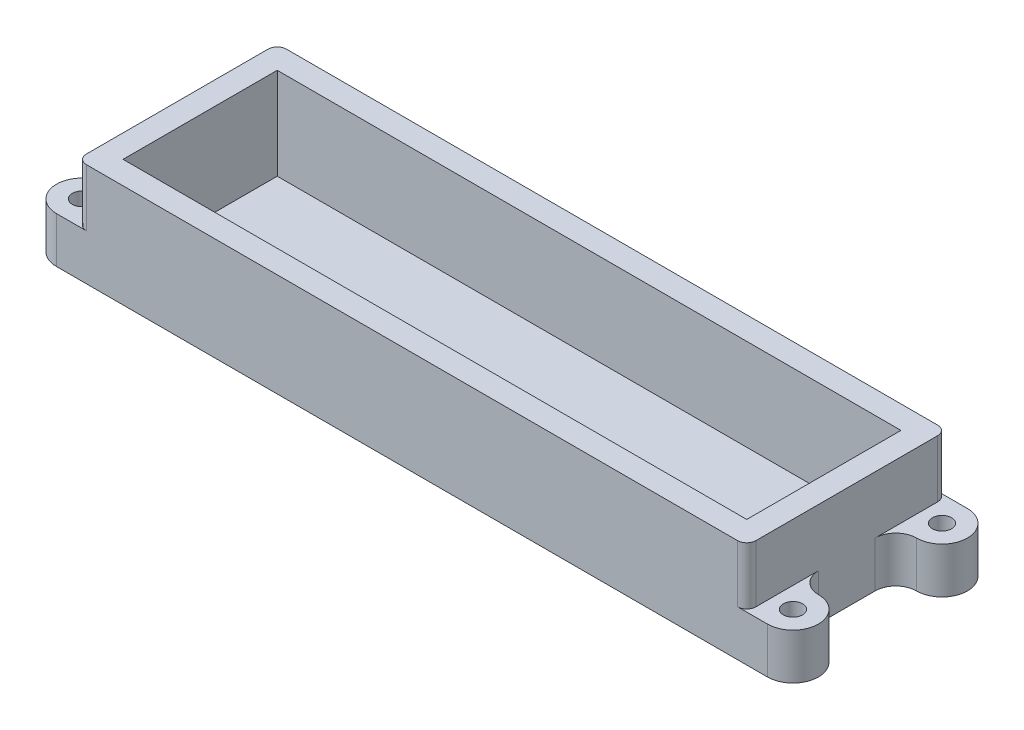
SolidWorks part; units mm, degrees
ref_plane "Front Plane" through (0, 0, 0) normal (0, 0, 1) x (1, 0, 0)
ref_plane "Top Plane" through (0, 0, 0) normal (0, 1, 0) x (1, 0, 0)
ref_plane "Right Plane" through (0, 0, 0) normal (1, 0, 0) x (0, 0, -1)
sketch "Sketch1" plane through (0, 0, 0) normal (0, 1, 0) x (1, 0, 0)
  line L0 (0, 0) -> (-5.725, 0)
  line L1 (0, 0) -> (185.4, 0)
  line L2 (0, 0) -> (0, 55.4)
  line L3 (0, 55.4) -> (185.4, 55.4)
  line L4 (185.4, 0) -> (185.4, 55.4)
  line L5 (6.35, 49.05) -> (179.05, 49.05)
  line L6 (6.35, 49.05) -> (6.35, 6.35)
  line L7 (6.35, 6.35) -> (179.05, 6.35)
  line L8 (179.05, 49.05) -> (179.05, 6.35)
  line L9 (0, 19.85) -> (0, 0)
  line L10 (6.35, 27.7) -> (10.8808, 27.7) construction
  line L11 (92.7, 49.05) -> (92.7, 30.1082) construction
  line L12 (0, 55.4) -> (-5.725, 55.4)
  line L13 (0, 35.55) -> (0, 55.4)
  line L14 (185.4, 19.85) -> (185.4, 0)
  line L15 (185.4, 0) -> (191.125, 0)
  line L16 (185.4, 35.55) -> (185.4, 55.4)
  line L17 (185.4, 55.4) -> (191.125, 55.4)
  circle A0 centre (42.7, 20.7) radius 3.175
  circle A1 centre (142.7, 20.7) radius 3.175
  arc A2 (-5.725, 0) -> (-5.725, 14.125) centre (-5.725, 7.0625) cw
  arc A3 (-5.725, 14.125) -> (0, 19.85) centre (-5.725, 19.85) ccw
  arc A4 (-5.725, 41.275) -> (0, 35.55) centre (-5.725, 35.55) cw
  arc A5 (-5.725, 55.4) -> (-5.725, 41.275) centre (-5.725, 48.3375) ccw
  circle A6 centre (-5.725, 7.0625) radius 2.667
  circle A7 centre (-5.725, 48.3375) radius 2.667
  circle A8 centre (191.125, 7.0625) radius 2.667
  circle A9 centre (191.125, 48.3375) radius 2.667
  arc A10 (191.125, 14.125) -> (185.4, 19.85) centre (191.125, 19.85) cw
  arc A11 (191.125, 0) -> (191.125, 14.125) centre (191.125, 7.0625) ccw
  arc A12 (191.125, 41.275) -> (185.4, 35.55) centre (191.125, 35.55) ccw
  arc A13 (191.125, 55.4) -> (191.125, 41.275) centre (191.125, 48.3375) cw
  point P9 (92.7, 49.05)
  point P10 (6.35, 27.7)
  point P11 (92.7, 27.7)
  point P44 (180.2689, 6.35)
  point P45 (181.9468, 42.173)
  dimension "D7" = 6.35
  dimension "D12" = 5.334
  dimension "D1" = 172.7
  dimension "D2" = 6.35
  dimension "D3" = 6.35
  dimension "D4" = 6.35
  dimension "D5" = 6.35
  dimension "D6" = 42.7
  dimension "D8" = 7
  dimension "D9" = 50
  dimension "D10" = 50
  dimension "D11" = 7
  dimension "D13" = 196.85
  dimension "D14" = 41.275
extrude "Boss-Extrude1" add sketch "Sketch1" along normal blind 3.175 contours L8 L5 L6 L7 A1 A0 | A0 | A1 region at (92.7, 0, -27.7606) region at (42.7, 0, -20.7) region at (142.7, 0, -20.7)
extrude "Boss-Extrude2" add sketch "Sketch1<3>" along normal blind 6.35 from surface contours A0 | A1 region at (42.7, 0, -20.7) region at (142.7, 0, -20.7) starting at face at (92.7, 3.175, -27.7)
sketch "Sketch1<3>" plane through (0, 0, 0) normal (0, 1, 0) x (1, 0, 0) same geometry as "Sketch1"
extrude "Boss-Extrude3" add sketch "Sketch1<4>" along normal offset from surface (28.575 mm away) 19.05 contours L1 L4 L3 L2 L5 L8 L7 L6 region at (1.935, 0, -9.925) up to face at (42.7, 9.525, -17.525) offset beyond the face yes
sketch "Sketch1<4>" plane through (0, 0, 0) normal (0, 1, 0) x (1, 0, 0) same geometry as "Sketch1"
extrude "Boss-Extrude4" add sketch "Sketch1<5>" along normal blind 12.7 contours A3 A2 L0 L2 A6 | L12 A5 A4 L2 A7 | L15 A11 A10 L4 A8 | A13 L17 L4 A12 A9 region at (-2.8625, 0, -0.2361) region at (185.6361, 0, -9.925) region at (-1.5098, 0, -39.7652) region at (185.6361, 0, -45.475)
sketch "Sketch1<5>" plane through (0, 0, 0) normal (0, 1, 0) x (1, 0, 0) same geometry as "Sketch1"
hole_wizard "M2x0.4 Tapped Hole1" positions "Sketch2" profile "Sketch4" tap size "M2x0.4" standard "ANSI Metric"
sketch "Sketch2" plane through (0, 9.525, 0) normal (0, 1, 0) x (1, 0, 0)
  point P0 (42.7, 20.7)
  point P3 (142.7, 20.7)
sketch "Sketch4" plane through (42.7, 9.525, -20.7) normal (1, 0, 0) x (0, 0, 1)
  line L0 (0, 0) -> (0, 5.6801)
  line L1 (0, 5.6801) -> (0.8, 5.1994)
  line L2 (0.8, 5.1994) -> (0.8, 0)
  line L5 (0.8, 0) -> (0, 0)
  line L10 (0, 5.6801) -> (-0.8, 5.1994) construction
  line L11 (0, -6.35) -> (0, 107.95) construction
  dimension "Tap Drill Dia." = 1.6
  dimension "Tap Drill Depth" = 5.1994
  dimension "Drill Angle" = 118
cosmetic thread "Hole Thread1" parameters "D1"=4.0005, "D2"=2
cosmetic thread "Hole Thread2" parameters "D1"=4.0005, "D2"=2
fillet "Fillet1" radius 2.54 4 edges at (0, 20.6375, 0) (0, 20.6375, -55.4) (185.4, 20.6375, 0) (185.4, 20.6375, -55.4)
